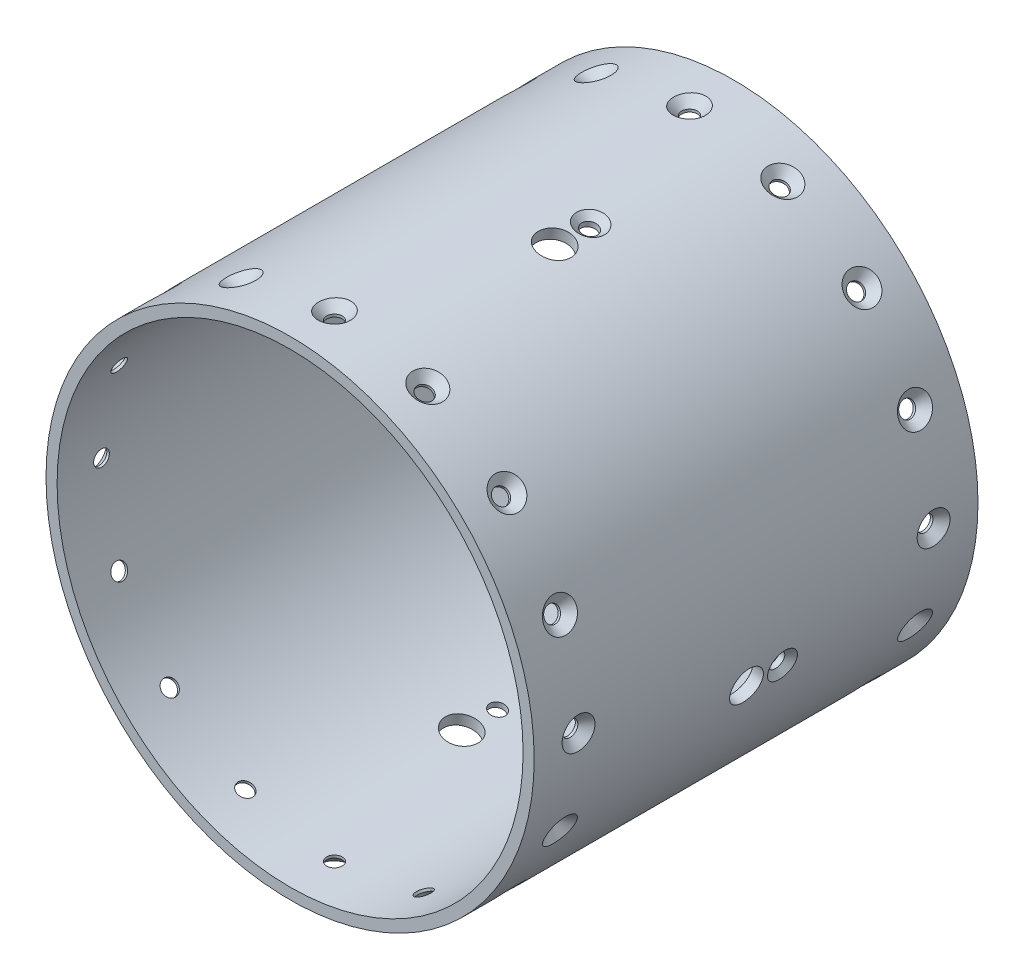
SolidWorks part; units mm, degrees
ref_plane "Front Plane" through (0, 0, 0) normal (0, 0, 1) x (1, 0, 0)
ref_plane "Top Plane" through (0, 0, 0) normal (0, 1, 0) x (1, 0, 0)
ref_plane "Right Plane" through (0, 0, 0) normal (1, 0, 0) x (0, 0, -1)
sketch "Sketch1" plane through (0, 0, 0) normal (0, 0, 1) x (1, 0, 0)
  circle A0 centre (0, 0) radius 66.675
  circle A1 centre (0, 0) radius 69.85
extrude "Extrude1" add sketch "Sketch1" along normal blind 127
sketch "Sketch4" plane through (0, 0, 0) normal (0, 0, -1) x (-1, 0, 0)
  circle A0 centre (0, 0) radius 66.675
sketch "Sketch5" plane through (0, 0, 127) normal (0, 0, 1) x (1, 0, 0)
  circle A0 centre (0, 0) radius 66.675
ref_plane "Plane1" through (0, 0, 12.7) normal (0, 0, 1) x (1, 0, 0)
ref_plane "Plane3" through (0, 0, 114.3) normal (0, 0, 1) x (1, 0, 0)
sketch "Sketch11" plane through (0, 0, 114.3) normal (0, 0, 1) x (1, 0, 0)
  line L0 (0, 0) -> (69.85, 0) construction
  circle A0 centre (0, 0) radius 69.85 construction
ref_plane "Plane4" through (69.85, 0, 114.3) normal (1, 0, 0) x (0, 0, -1)
hole_wizard "CSK for M4 Flat Head Machine Screw1" positions "Sketch13" profile "Sketch12" countersink size "M4" standard "Ansi Metric"
sketch "Sketch13" plane through (69.85, 0, 114.3) normal (1, 0, 0) x (0, 0, -1)
  point P1 (0, 0)
sketch "Sketch12" plane through (69.85, 0, 114.3) normal (0, 1, 0) x (0, 0, -1)
  line L0 (0, 0) -> (0, 13.5439)
  line L1 (0, 13.5439) -> (2.25, 12.192)
  line L2 (2.25, 12.192) -> (2.25, 2.45)
  line L3 (2.25, 2.45) -> (4.7, 0)
  line L5 (4.7, 0) -> (0, 0)
  line L6 (-2.25, 2.45) -> (-4.7, 0) construction
  line L10 (0, 13.5439) -> (-2.25, 12.192) construction
  line L11 (0, -6.35) -> (0, 107.95) construction
  dimension "Hole Dia." = 4.5
  dimension "Hole Depth" = 12.192
  dimension "Near C'Sink Dia." = 9.4
  dimension "Near C'Sink Angle" = 90
  dimension "Drill Angle" = 118
sketch "Sketch23" plane through (0, 0, 12.7) normal (0, 0, 1) x (1, 0, 0)
  line L0 (0, 0) -> (69.85, 0) construction
ref_plane "Plane7" through (69.85, 0, 12.7) normal (1, 0, 0) x (0, 0, -1)
hole_wizard "CSK for M4 Flat Head Machine Screw2" positions "Sketch29" profile "Sketch30" countersink size "M4" standard "Ansi Metric"
sketch "Sketch29" plane through (69.85, 0, 12.7) normal (1, 0, 0) x (0, 0, -1)
  point P1 (0, 0)
sketch "Sketch30" plane through (69.85, 0, 12.7) normal (0, 1, 0) x (0, 0, -1)
  line L0 (0, 0) -> (0, 13.5439)
  line L1 (0, 13.5439) -> (2.25, 12.192)
  line L2 (2.25, 12.192) -> (2.25, 2.45)
  line L3 (2.25, 2.45) -> (4.7, 0)
  line L5 (4.7, 0) -> (0, 0)
  line L6 (-2.25, 2.45) -> (-4.7, 0) construction
  line L10 (0, 13.5439) -> (-2.25, 12.192) construction
  line L11 (0, -6.35) -> (0, 107.95) construction
  dimension "Hole Dia." = 4.5
  dimension "Hole Depth" = 12.192
  dimension "Near C'Sink Dia." = 9.4
  dimension "Near C'Sink Angle" = 90
  dimension "Drill Angle" = 118
pattern_circular "CirPattern1" count 16 over 360 about axis through (0, 0, 127) along (0, 0, -1) of "CSK for M4 Flat Head Machine Screw1", "CSK for M4 Flat Head Machine Screw2"
ref_plane "Plane8" through (0, 0, 64.77) normal (0, 0, 1) x (1, 0, 0)
sketch "Sketch35" plane through (0, 0, 64.77) normal (0, 0, 1) x (1, 0, 0)
  line L0 (69.7734, 0) -> (67.4, 0) construction
  arc A0 (69.85, 0) -> (68.5079, -13.6271) centre (0, 0) cw
  circle A1 centre (0, 0) radius 69.85 construction
sketch "Sketch31" plane through (0, 0, 64.77) normal (0, 0, 1) x (1, 0, 0)
  line L0 (0, 0) -> (68.5079, -13.6271) construction
ref_plane "Plane6" through (68.5079, -13.6271, 64.77) normal (0.9808, -0.1951, 0) x (0.1951, 0.9808, 0)
sketch "Sketch15" plane through (68.5079, -13.6271, 64.77) normal (0.9808, -0.1951, 0) x (0.1951, 0.9808, 0)
  line L0 (0, 0.1207) -> (0, -10.16) construction
hole_wizard "3/8 (0.375) Diameter Hole1" positions "Sketch33" profile "Sketch32" hole size "3/8" standard "Ansi Inch"
sketch "Sketch33" plane through (68.5079, -13.6271, 64.77) normal (0.9808, -0.1951, 0) x (0.1951, 0.9808, 0)
  point P1 (0, 0.1207)
sketch "Sketch32" plane through (68.5079, -13.6271, 64.8907) normal (0, 0, 1) x (0.1951, 0.9808, 0)
  line L0 (0, 0) -> (0, 15.5616)
  line L1 (0, 15.5616) -> (4.7625, 12.7)
  line L2 (4.7625, 12.7) -> (4.7625, 0)
  line L5 (4.7625, 0) -> (0, 0)
  line L10 (0, 15.5616) -> (-4.7625, 12.7) construction
  line L11 (0, -6.35) -> (0, 107.95) construction
  dimension "Hole Dia." = 9.525
  dimension "Hole Depth" = 12.7
  dimension "Drill Angle" = 118
hole_wizard "CSK for #8 Flat Head Machine Screw (100)2" positions "Sketch21" profile "Sketch22" countersink size "#8" standard "Ansi Inch"
sketch "Sketch21" plane through (68.5079, -13.6271, 64.77) normal (0.9808, -0.1951, 0) x (0.1951, 0.9808, 0)
  point P1 (0, -10.16)
sketch "Sketch22" plane through (68.5079, -13.6271, 54.61) normal (0, 0, 1) x (0.1951, 0.9808, 0)
  line L0 (0, 0) -> (0, 13.5427)
  line L1 (0, 13.5427) -> (2.2479, 12.192)
  line L2 (2.2479, 12.192) -> (2.2479, 1.6518)
  line L3 (2.2479, 1.6518) -> (4.2164, 0)
  line L5 (4.2164, 0) -> (0, 0)
  line L6 (-2.2479, 1.6518) -> (-4.2164, 0) construction
  line L10 (0, 13.5427) -> (-2.2479, 12.192) construction
  line L11 (0, -6.35) -> (0, 107.95) construction
  dimension "Hole Dia." = 4.4958
  dimension "Hole Depth" = 12.192
  dimension "Near C'Sink Dia." = 8.4328
  dimension "Near C'Sink Angle" = 100
  dimension "Drill Angle" = 118
pattern_circular "CirPattern2" count 4 over 360 about axis through (0, 0, 127) along (0, 0, -1) of "CSK for #8 Flat Head Machine Screw (100)2", "3/8 (0.375) Diameter Hole1"
